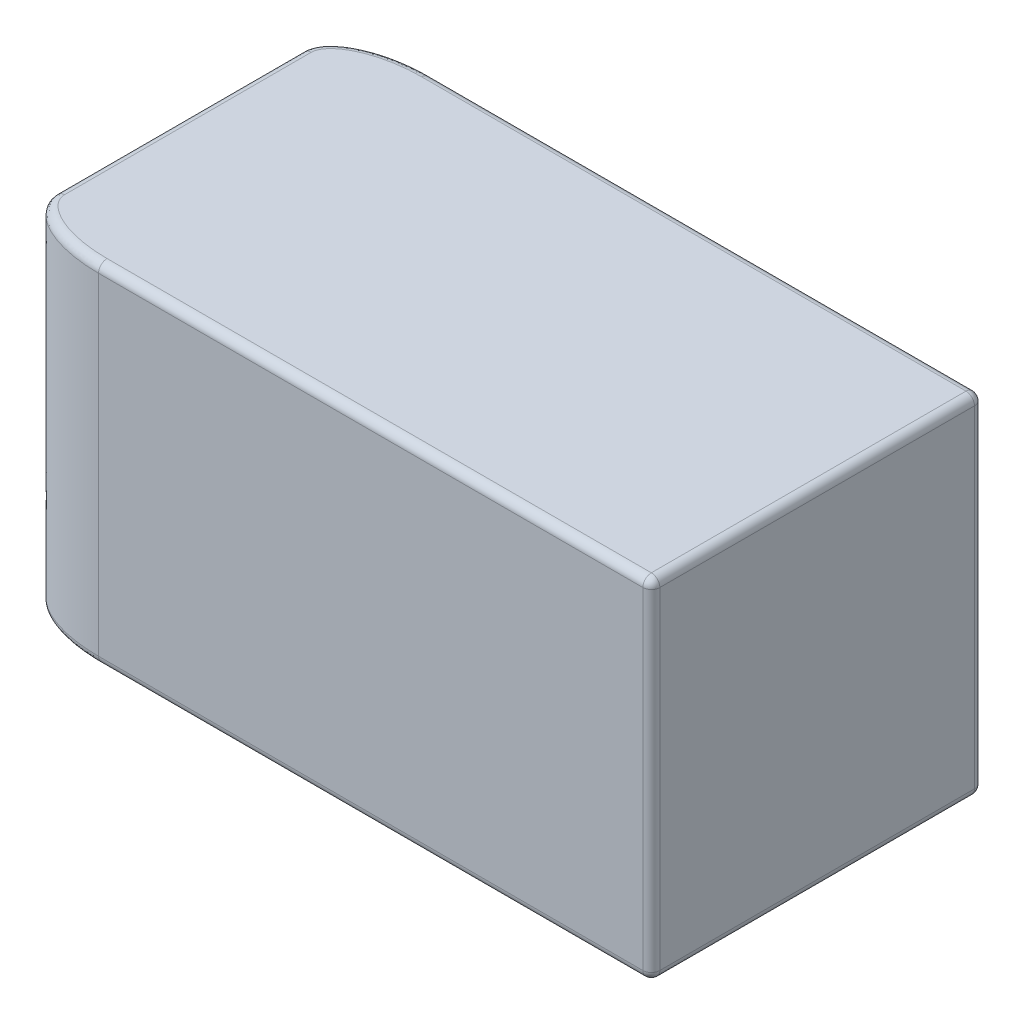
SolidWorks part; units mm, degrees
material "Rubber"
ref_plane "Front Plane" through (0, 0, 0) normal (0, 0, 1) x (1, 0, 0)
ref_plane "Top Plane" through (0, 0, 0) normal (0, 1, 0) x (1, 0, 0)
ref_plane "Right Plane" through (0, 0, 0) normal (1, 0, 0) x (0, 0, -1)
sketch "Sketch1" plane through (0, 0, 0) normal (0, 1, 0) x (1, 0, 0)
  line L1 (-37.5, -19.5) -> (37.5, -19.5)
  line L2 (-37.5, -19.5) -> (-37.5, 19.5)
  line L3 (-37.5, 19.5) -> (37.5, 19.5)
  line L4 (37.5, -19.5) -> (37.5, 19.5)
  line L5 (-37.5, -19.5) -> (37.5, 19.5) construction
  line L6 (-37.5, 19.5) -> (37.5, -19.5) construction
  point P0 (0, 0)
  dimension "D1" = 39
  dimension "D2" = 75
extrude "Boss-Extrude1" add sketch "Sketch1" along normal mid plane 41
fillet "Fillet1" radius 1 2 edges at (37.5, 0, -19.5) (37.5, 0, 19.5)
fillet "Fillet2" radius 5 2 edges at (-37.5, 0, -19.5) (-37.5, 0, 19.5) second distance 10 first distance on face at (-37.5, 0, 0)
fillet "Fillet3" radius 1 16 edges at (37.2071, -20.5, -19.2071) (37.5, -20.5, 0) (37.2071, -20.5, 19.2071) (37.2071, 20.5, -19.2071) (37.5, 20.5, 0) (37.2071, 20.5, 19.2071)
